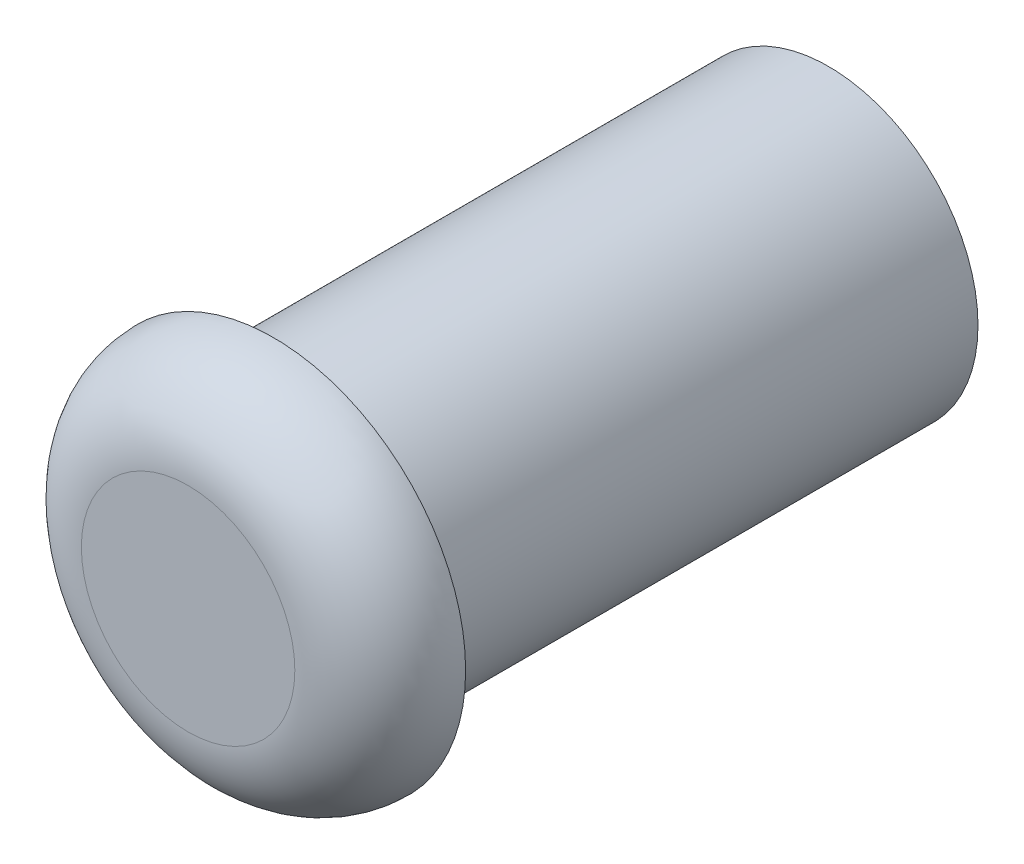
SolidWorks part; units mm, degrees
material "Hierro dúctil"
ref_plane "Alzado" through (0, 0, 0) normal (0, 0, 1) x (1, 0, 0)
ref_plane "Planta" through (0, 0, 0) normal (0, 1, 0) x (1, 0, 0)
ref_plane "Vista lateral" through (0, 0, 0) normal (1, 0, 0) x (0, 0, -1)
sketch "Croquis1" plane through (0, 0, 0) normal (0, 0, 1) x (1, 0, 0)
  circle A0 centre (0, 0) radius 3.5
  dimension "D1" = 7
extrude "Saliente-Extruir1" add sketch "Croquis1" along normal blind 13
sketch "Croquis2" plane through (0, 0, 13) normal (0, 0, 1) x (1, 0, 0)
  circle A0 centre (0, 0) radius 4.5
  dimension "D1" = 9
extrude "Saliente-Extruir2" add sketch "Croquis2" along normal blind 2
fillet "Redondeo1" radius 2 1 edges at (4.5, 0, 15)
